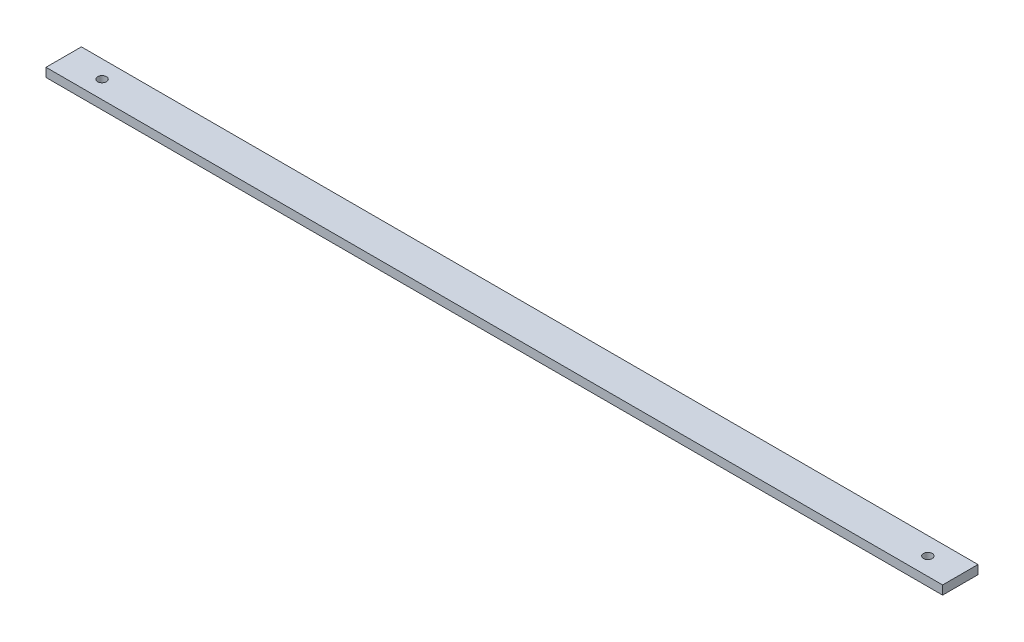
SolidWorks part; units mm, degrees
ref_plane "Front Plane" through (0, 0, 0) normal (0, 0, 1) x (1, 0, 0)
ref_plane "Top Plane" through (0, 0, 0) normal (0, 1, 0) x (1, 0, 0)
ref_plane "Right Plane" through (0, 0, 0) normal (1, 0, 0) x (0, 0, -1)
ref_plane "Plane1" through (0, 3, 0) normal (0, 1, 0) x (1, 0, 0)
sketch "Sketch1" plane through (0, 3, 0) normal (0, 1, 0) x (1, 0, 0)
  line L0 (152, 6) -> (-152, 6)
  line L1 (-152, 6) -> (-152, -6)
  line L2 (-152, -6) -> (152, -6)
  line L3 (152, -6) -> (152, 6)
  circle A0 centre (-139, 0) radius 1.5
  circle A1 centre (141, 0) radius 1.5
extrude "Boss-Extrude1" add sketch "Sketch1" against normal blind 3
